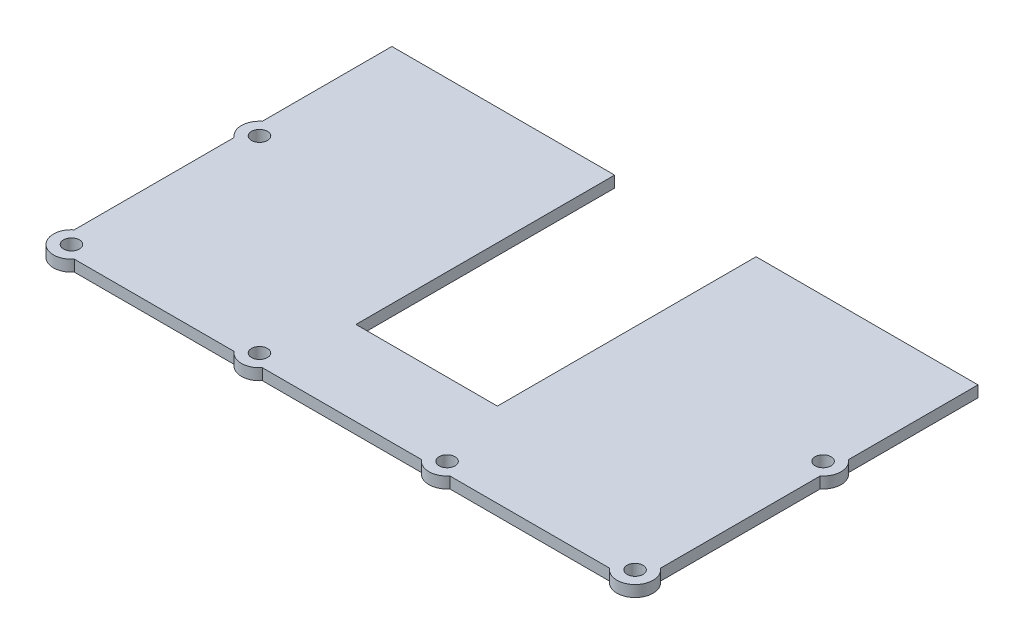
SolidWorks part; units mm, degrees
material "UHMW"
ref_plane "Front Plane" through (0, 0, 0) normal (0, 0, 1) x (1, 0, 0)
ref_plane "Top Plane" through (0, 0, 0) normal (0, 1, 0) x (1, 0, 0)
ref_plane "Right Plane" through (0, 0, 0) normal (1, 0, 0) x (0, 0, -1)
sketch "Sketch1" plane through (0, 0, 0) normal (0, 1, 0) x (1, 0, 0)
  circle A0 centre (3.175, -40.4401) radius 2.2479
  circle A1 centre (3.175, -93.3568) radius 2.2479
  circle A2 centre (56.0917, -93.3568) radius 2.2479
  circle A3 centre (108.8828, -93.3568) radius 2.2479
  circle A4 centre (161.7995, -93.3568) radius 2.2479
  circle A5 centre (161.7995, -40.4401) radius 2.2479
  point P13 (102.5193, -72.8218)
  line B0 (62.7063, 0) -> (0, 0)
  line B1 (62.7063, 0) -> (62.7063, -72.8218)
  line B2 (164.9745, -36.4745) -> (164.9745, 0)
  line B3 (164.9745, -89.3912) -> (164.9745, -44.4057)
  line B4 (112.8484, -96.5318) -> (157.8339, -96.5318)
  line B5 (101.6, -96.5318) -> (104.9173, -96.5318)
  line B6 (101.6, -96.5318) -> (95.25, -96.5318)
  line B7 (69.85, -96.5318) -> (95.25, -96.5318)
  line B8 (69.85, -96.5318) -> (63.5, -96.5318)
  line B9 (60.0572, -96.5318) -> (63.5, -96.5318)
  line B10 (7.1406, -96.5318) -> (52.1261, -96.5318)
  line B11 (0, -44.4057) -> (0, -89.3912)
  line B12 (0, 0) -> (0, -36.4745)
  line B13 (164.9745, 0) -> (102.5193, 0)
  line B14 (102.5193, 0) -> (102.5193, -72.8218)
  line B15 (62.7063, -72.8218) -> (102.5193, -72.8218)
  arc B16 (164.9745, -44.4057) -> (164.9745, -36.4745) centre (161.7995, -40.4401) ccw
  arc B17 (157.8339, -96.5318) -> (164.9745, -89.3912) centre (161.7995, -93.3568) ccw
  arc B18 (104.9173, -96.5318) -> (112.8484, -96.5318) centre (108.8828, -93.3568) ccw
  arc B19 (52.1261, -96.5318) -> (60.0572, -96.5318) centre (56.0917, -93.3568) ccw
  arc B20 (0, -89.3912) -> (7.1406, -96.5318) centre (3.175, -93.3568) ccw
  arc B21 (0, -36.4745) -> (0, -44.4057) centre (3.175, -40.4401) ccw
  dimension "D1" = 4.4958
sketch_block_instance "Block-topplate-1"
sketch_block "Block-topplate"
extrude "Boss-Extrude1" add sketch "Sketch1" along normal blind 3.175
equation "\"Unit Measure\"= \"BoundingVolume\" / \"Thickness\"'in^2"
